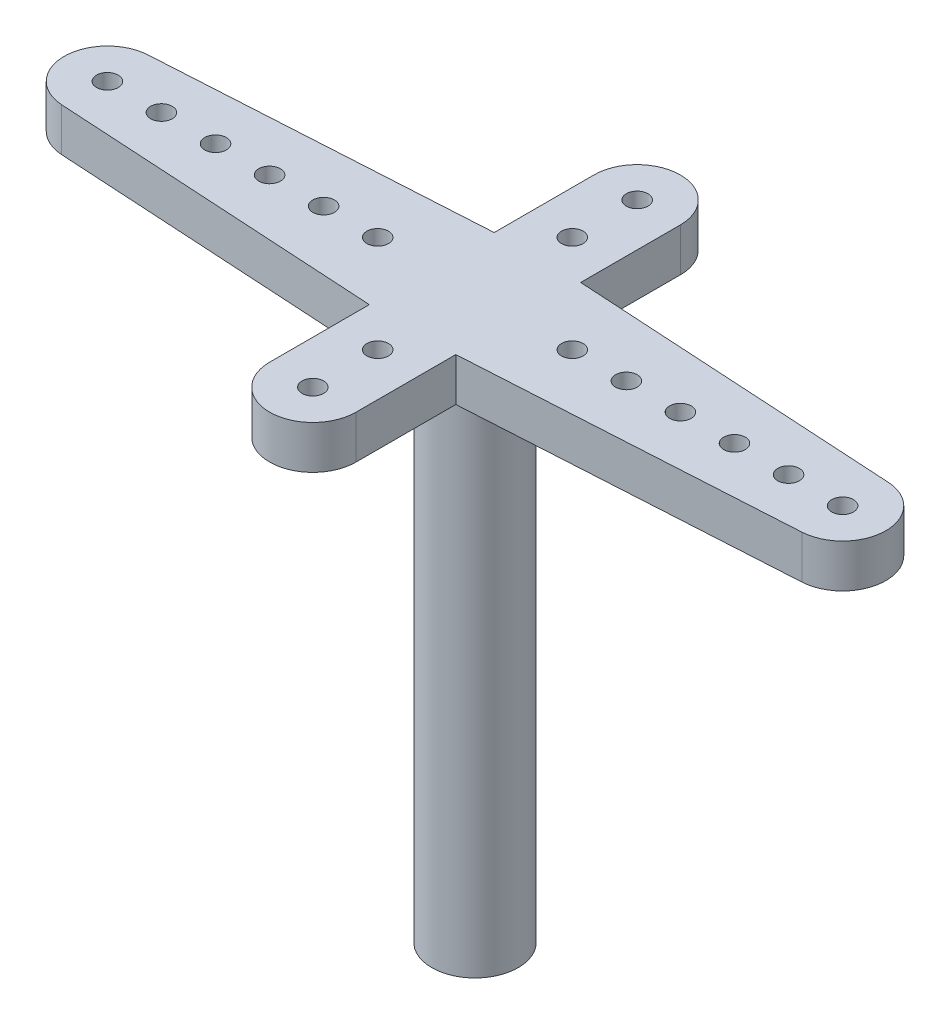
SolidWorks part; units mm, degrees
material "ABS"
ref_plane "Front Plane" through (0, 0, 0) normal (0, 0, 1) x (1, 0, 0)
ref_plane "Top Plane" through (0, 0, 0) normal (0, 1, 0) x (1, 0, 0)
ref_plane "Right Plane" through (0, 0, 0) normal (1, 0, 0) x (0, 0, -1)
sketch "Sketch1" plane through (0, 0, 0) normal (0, 1, 0) x (1, 0, 0)
  line L0 (-36.3167, 0) -> (36.3167, 0) construction
  line L1 (0, 19.7064) -> (0, -19.7064) construction
  line L2 (2, 7.5) -> (2, 2.8874)
  line L3 (17.1176, 1.9965) -> (2, 2.8874)
  line L4 (17.1176, -1.9965) -> (2, -2.8874)
  line L5 (-17.1176, -1.9965) -> (-2, -2.8874)
  line L6 (-17.1176, 1.9965) -> (-2, 2.8874)
  line L7 (-2, 7.5) -> (-2, 2.8874)
  line L8 (2, -7.5) -> (2, -2.8874)
  line L9 (-2, -7.5) -> (-2, -2.8874)
  line L10 (-2, 2.8874) -> (-0.1765, 2.9948) construction
  line L11 (2, 2.8874) -> (0.1765, 2.9948) construction
  line L12 (2, -2.8874) -> (0.1765, -2.9948) construction
  line L13 (-2, -2.8874) -> (-0.1765, -2.9948) construction
  circle A0 centre (0, 0) radius 2
  arc A1 (17.1176, 1.9965) -> (17.1176, -1.9965) centre (17, 0) cw
  arc A2 (-2, 7.5) -> (2, 7.5) centre (0, 7.5) cw
  circle A3 centre (0, 0) radius 3 construction
  arc A4 (-17.1176, 1.9965) -> (-17.1176, -1.9965) centre (-17, 0) ccw
  arc A5 (-2, -7.5) -> (2, -7.5) centre (0, -7.5) ccw
  circle A7 centre (-17, 0) radius 0.5
  circle A8 centre (17, 0) radius 0.5
  circle A9 centre (-14.5, 0) radius 0.5
  circle A10 centre (-12, 0) radius 0.5
  circle A11 centre (-9.5, 0) radius 0.5
  circle A12 centre (-7, 0) radius 0.5
  circle A13 centre (-4.5, 0) radius 0.5
  circle A14 centre (4.5, 0) radius 0.5
  circle A15 centre (7, 0) radius 0.5
  circle A16 centre (9.5, 0) radius 0.5
  circle A17 centre (12, 0) radius 0.5
  circle A18 centre (14.5, 0) radius 0.5
  circle A19 centre (0, 7.5) radius 0.5
  circle A20 centre (0, 4.5) radius 0.5
  circle A21 centre (0, -4.5) radius 0.5
  circle A22 centre (0, -7.5) radius 0.5
  point P6 (0, 0)
  point P9 (0, 0)
  dimension "D1" = 4
  dimension "D3" = 2
  dimension "D5" = 2
  dimension "D6" = 6
  dimension "D7" = 1
  dimension "D9" = 4.5
  dimension "D10" = 1
  dimension "D2" = 17
  dimension "D4" = 7.5
  dimension "D12" = 4.5
  dimension "D8" = 6
  dimension "D11" = 2
extrude "Boss-Extrude1" add sketch "Sketch1" along normal blind 2
extrude "Boss-Extrude2" add sketch "Sketch1<3>" against normal blind 26 from surface contours A0 region at (0, 0, 0) starting at face at (0, 2, 0)
sketch "Sketch1<3>" plane through (0, 0, 0) normal (0, 1, 0) x (1, 0, 0) same geometry as "Sketch1"
